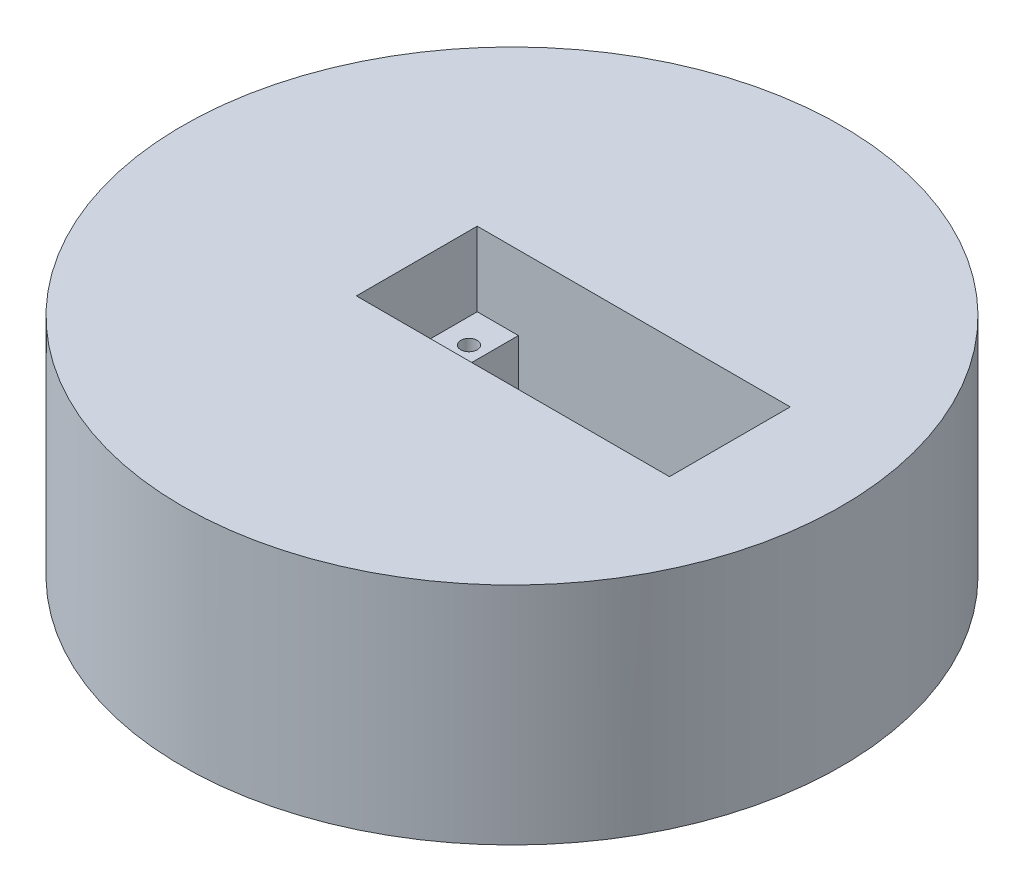
SolidWorks part; units mm, degrees
ref_plane "Front Plane" through (0, 0, 0) normal (0, 0, 1) x (1, 0, 0)
ref_plane "Top Plane" through (0, 0, 0) normal (0, 1, 0) x (1, 0, 0)
ref_plane "Right Plane" through (0, 0, 0) normal (1, 0, 0) x (0, 0, -1)
sketch "Sketch1" plane through (0, 0, 0) normal (0, 1, 0) x (1, 0, 0)
  line L0 (-21, 0) -> (-11.17, 0) construction
  line L1 (21, -11) -> (-21, -11)
  line L2 (21, -11) -> (21, 11)
  line L3 (21, 11) -> (-21, 11)
  line L4 (-21, -11) -> (-21, 11)
  line L5 (21, -11) -> (-21, 11) construction
  line L6 (21, 11) -> (-21, -11) construction
  line L7 (-24, 5) -> (-24, -5) construction
  line L8 (28.5, -11) -> (-28.5, -11)
  line L9 (28.5, -11) -> (28.5, 11)
  line L10 (28.5, 11) -> (-28.5, 11)
  line L11 (-28.5, -11) -> (-28.5, 11)
  line L12 (28.5, -11) -> (-28.5, 11) construction
  line L13 (28.5, 11) -> (-28.5, -11) construction
  line L14 (0, 6.218) -> (0, -5.9998) construction
  line L15 (24, 5) -> (24, -5) construction
  line L16 (-24, 5) -> (24, 5) construction
  circle A0 centre (-11.17, 0) radius 2.5
  circle A1 centre (-11.17, 0) radius 60
  circle A2 centre (-24, 5) radius 1.5
  circle A3 centre (-24, -5) radius 1.5
  circle A4 centre (24, -5) radius 1.5
  circle A5 centre (24, 5) radius 1.5
  point P0 (0, 0)
  point P10 (0, 0)
  point P17 (-24, 0)
  dimension "D4" = 5
  dimension "D5" = 120
  dimension "D8" = 3
  dimension "D1" = 42
  dimension "D2" = 22
  dimension "D3" = 9.83
  dimension "D6" = 57
  dimension "D7" = 10
  dimension "D9" = 48
extrude "Boss-Extrude2" add sketch "Sketch1" along normal blind 27.5 contours L11 L8 L4 L10 A3 A2 | L9 L10 L2 L8 A4 A5 region at (24.8203, 0, 0) region at (-24.8203, 0, 0)
extrude "Boss-Extrude3" add sketch "Sketch1<5>" along normal blind 41 contours A1 L8 L11 L10 L3 L9 L1 region at (-69.4729, 0, 0)
sketch "Sketch1<5>" plane through (0, 0, 0) normal (0, 1, 0) x (1, 0, 0) same geometry as "Sketch1"
extrude "Cut-Extrude1" cut sketch "Sketch1<7>" along normal blind 15 contours L9 L10 L2 L8 A4 A5 | L11 L8 L4 L10 A3 A2 region at (24.8203, 0, 0) region at (-24.8203, 0, 0)
sketch "Sketch1<7>" plane through (0, 0, 0) normal (0, 1, 0) x (1, 0, 0) same geometry as "Sketch1"
sketch "Sketch2" plane through (0, 0, 0) normal (0, -1, 0) x (1, 0, 0)
  line L0 (28.5, -11) -> (-28.5, -11) construction
  line L1 (-28.5, 11) -> (-84.8588, 11)
  line L2 (-28.5, 11) -> (-28.5, -11)
  line L3 (-28.5, -11) -> (-84.8588, -11)
  line L4 (-84.8588, 11) -> (-84.8588, -11)
extrude "Cut-Extrude2" cut sketch "Sketch2" against normal blind 15
sketch "Sketch3" plane through (0, 41, 0) normal (0, 1, 0) x (1, 0, 0)
  circle A0 centre (-11.17, 0) radius 60
